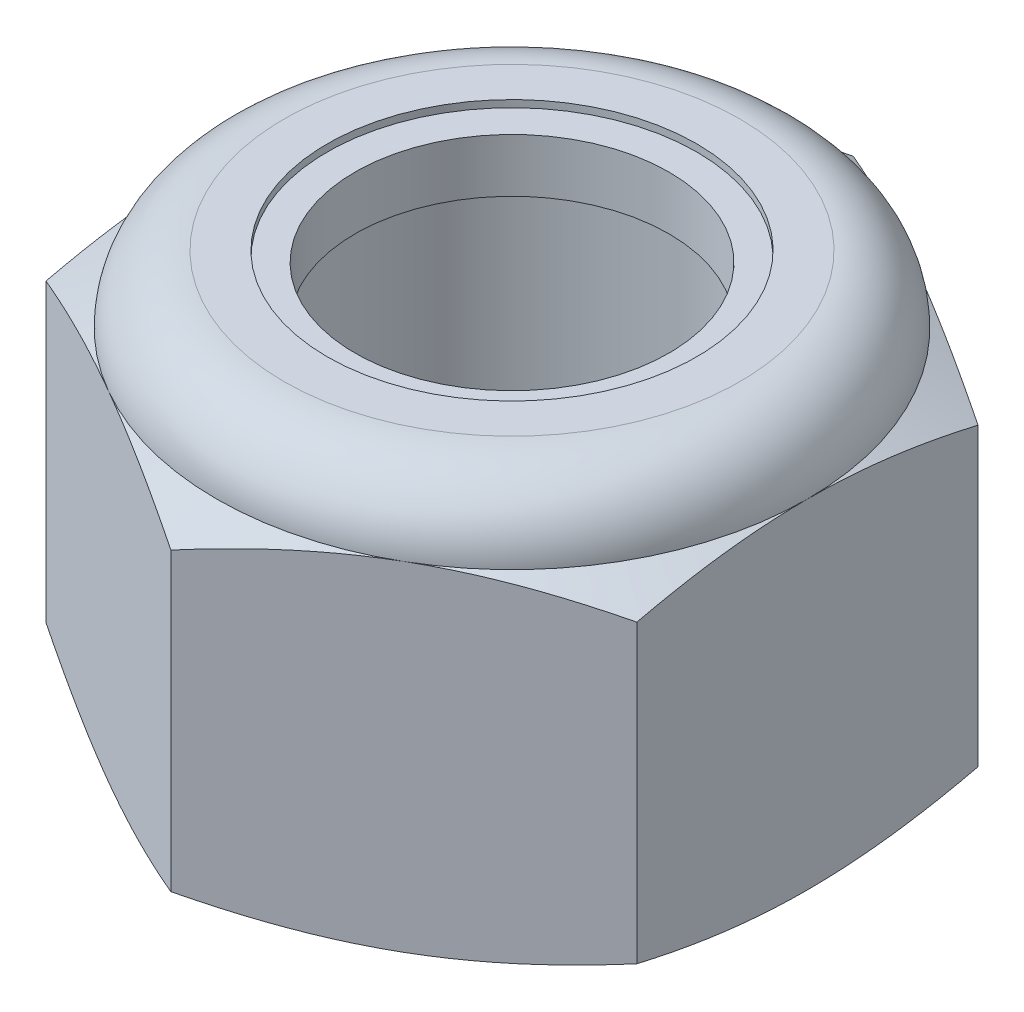
SolidWorks part; units mm, degrees
ref_plane "Front" through (0, 0, 0) normal (0, 0, 1) x (1, 0, 0)
ref_plane "Top" through (0, 0, 0) normal (0, 1, 0) x (1, 0, 0)
ref_plane "Right" through (0, 0, 0) normal (1, 0, 0) x (0, 0, -1)
sketch "Sketch1" plane through (0, 0, 0) normal (1, 0, 0) x (0, 0, -1)
  line L0 (0, 0) -> (0, 8.7312) construction
  line L1 (6.35, 0) -> (-6.35, 0) construction
  line L2 (-3.9688, 8.7312) -> (3.9688, 8.7312) construction
  line L3 (3.9688, 8.7312) -> (3.9687, 7.6729) construction
  point P9 (-3.9688, 8.7312)
  point P10 (3.9688, 8.7312)
  point P11 (6.35, 0)
  dimension "Height" = 8.7312
  dimension "Hex Flats" = 12.7
  dimension "Thread Dia" = 7.9375
  dimension "Thread Pitch" = 1.0583
sketch "Sketch13" plane through (0, 0, 0) normal (0, 1, 0) x (1, 0, 0)
  line L1 (0, 7.3323) -> (-6.35, 3.6662)
  line L2 (-6.35, 3.6662) -> (-6.35, -3.6662)
  line L3 (-6.35, -3.6662) -> (0, -7.3323)
  line L4 (0, -7.3323) -> (6.35, -3.6662)
  line L5 (6.35, -3.6662) -> (6.35, 3.6662)
  line L6 (6.35, 3.6662) -> (0, 7.3323)
  circle A0 centre (0, 0) radius 6.35 construction
  circle A1 centre (0, 0) radius 3.9688
  point P11 (0, -3.9688)
  point P13 (0, 3.9688)
extrude "Extrude1" add sketch "Sketch13" along normal up to vertex (8.7312 mm away) up to point (0, 8.7312, 0)
sketch "Sketch5" plane through (0, 0, 0) normal (1, 0, 0) x (0, 0, -1)
  line L0 (0, 0) -> (6.35, 0)
  line L1 (6.35, 0) -> (7.3323, 0.4581)
  line L2 (7.3323, 0.4581) -> (7.3323, 6.818)
  line L3 (7.3323, 6.818) -> (6.35, 7.276)
  line L4 (4.8948, 8.7312) -> (4.8948, 10.0013)
  line L5 (4.8948, 10.0013) -> (8.6023, 10.0013)
  line L6 (8.6023, 10.0013) -> (8.6023, -1.27)
  line L7 (8.6023, -1.27) -> (0, -1.27)
  line L8 (0, -1.27) -> (0, 0)
  line L9 (6.35, 7.276) -> (6.35, 0) construction
  line L12 (7.3323, 8.7312) -> (7.3323, 0) construction
  line L13 (7.3323, 4.3656) -> (8.6023, 4.3656) construction
  line L15 (0, 0) -> (0, 10.0013) construction
  line L18 (6.35, 0) -> (-6.35, 0) construction
  line L19 (3.6662, 8.7312) -> (7.3323, 8.7312) construction
  line L20 (0, 10.0013) -> (4.8948, 10.0013) construction
  line L21 (3.6662, 0) -> (7.3323, 0) construction
  arc A0 (6.35, 7.276) -> (4.8948, 8.7312) centre (4.8948, 7.276) ccw
  dimension "D1" = 25
  dimension "D2" = 1.27
  dimension "D4" = 1.4552
revolve "Cut-Revolve3" cut sketch "Sketch5" angle 360 about L15
sketch "Sketch4" plane through (0, 0, 0) normal (1, 0, 0) x (0, 0, -1)
  line L0 (0, 7.276) -> (4.3656, 7.276)
  line L1 (4.3656, 7.276) -> (0, 5.2403)
  line L3 (0, 2.0357) -> (4.3656, 0)
  line L4 (4.3656, 0) -> (0, 0)
  line L5 (0, 0) -> (0, 7.276) construction
  line L10 (0, 0) -> (0, 8.7312) construction
  line L11 (0, 2.0357) -> (0, 0)
  line L12 (0, 7.276) -> (0, 5.2403)
  line L13 (5.4993, 7.276) -> (0, 7.276) construction
  dimension "D1" = 25
  dimension "D2" = 8.7312
sketch "Sketch6" plane through (0, 0, 0) normal (1, 0, 0) x (0, 0, -1)
  line L0 (0, 7.276) -> (6.1976, 7.276)
  line L1 (4.8948, 8.5788) -> (2.4474, 8.5788)
  line L2 (0, 10.0013) -> (0, 7.276)
  line L3 (2.4474, 10.0013) -> (0, 10.0013)
  line L4 (0, 10.0013) -> (4.8948, 10.0013) construction
  line L5 (0, 0) -> (0, 10.0013) construction
  line L6 (0, 10.0013) -> (0, 0) construction
  line L7 (2.4474, 8.5788) -> (2.4474, 10.0013)
  line L8 (4.8948, 8.7312) -> (4.8948, 8.5788) construction
  line L9 (2.4474, 8.5788) -> (0, 8.5788) construction
  line L10 (0, 8.5788) -> (0, 5.2403) construction
  arc A0 (6.1976, 7.276) -> (4.8948, 8.5788) centre (4.8948, 7.276) ccw
  arc A1 (6.35, 7.276) -> (4.8948, 8.7312) centre (4.8948, 7.276) ccw construction
  dimension "D1" = 0.1524
revolve "Cut-Revolve4" cut sketch "Sketch6" angle 360 about L6
revolve "Cut-Revolve2" cut sketch "Sketch4" angle 360 about L5
sketch "Sketch7" plane through (0, 0, 0) normal (1, 0, 0) x (0, 0, -1)
  line L0 (3.3734, 7.3522) -> (6.119, 7.3522)
  line L1 (4.8948, 8.5027) -> (3.3734, 8.5027)
  line L2 (3.3734, 8.5027) -> (3.3734, 7.3522)
  line L3 (3.3734, 7.3522) -> (0, 7.3522) construction
  line L4 (0, 7.3522) -> (0, 8.5027) construction
  line L5 (0, 8.5027) -> (3.3734, 8.5027) construction
  line L6 (3.3734, 7.3522) -> (3.3734, 7.276) construction
  line L7 (0, 7.276) -> (6.1976, 7.276) construction
  line L8 (4.8948, 8.5027) -> (4.8948, 8.5788) construction
  arc A0 (6.119, 7.3522) -> (4.8948, 8.5027) centre (4.8948, 7.276) ccw
  arc A2 (6.1976, 7.276) -> (4.8948, 8.5788) centre (4.8948, 7.276) ccw construction
  point P15 (3.3734, 8.5027)
  point P18 (-4.1341, 8.5027)
  point P19 (4.1341, 8.5027)
  dimension "D2" = 6.7469
revolve "Revolve2" add sketch "Sketch7" angle 360 about L4
sketch "Sketch2" [suppressed] plane through (0, 0, 0) normal (1, 0, 0) x (0, 0, -1)
  line L0 (-3.9688, 0) -> (-3.9688, 7.276) construction
  line L1 (0, 0) -> (3.9688, 0)
  line L2 (0, 0) -> (0, 7.276)
  line L3 (0, 7.276) -> (3.9688, 7.276)
  line L4 (3.9688, 0) -> (3.9688, 7.276)
  line L6 (5.4993, 7.276) -> (6.35, 7.276) construction
  line L7 (0, -3.9688) -> (0, 0) construction
revolve "Revolve1" [suppressed] add sketch "Sketch2" angle 360 about L7
sketch "Sketch9" [suppressed] plane through (0, 0, 0) normal (1, 0, 0) x (0, 0, -1)
  line L0 (4.0833, 8.2682) -> (4.0833, 7.2099) construction
  line L1 (4.0833, 7.2099) -> (3.1668, 7.7391) construction
  line L2 (3.1668, 7.7391) -> (4.0833, 8.2682) construction
  line L3 (3.2813, 7.8052) -> (3.2813, 7.6729) construction
  line L4 (3.9688, 8.2021) -> (3.9688, 7.276) construction
  line L5 (3.1668, 7.7391) -> (3.2813, 7.7391) construction
  line L6 (3.9688, 7.7391) -> (4.0833, 7.7391) construction
  line L7 (4.026, 7.7391) -> (4.026, 8.2352) construction
  line L8 (4.0833, 7.2099) -> (4.026, 8.2352)
  line L9 (4.026, 8.2352) -> (3.2813, 7.8052)
  line L10 (3.2813, 7.8052) -> (3.2813, 7.6729)
  line L11 (3.2813, 7.6729) -> (4.0833, 7.2099)
  dimension "D1" = 1.0583
  dimension "D2" = 0.1323
sketch "Sketch10" [suppressed] plane through (0, 7.276, 0) normal (0, 1, 0) x (1, 0, 0)
  circle A1 centre (0, 0) radius 3.9688
  circle A2 centre (0, 0) radius 3.9688
  dimension "D1" = 0
curve "Helix/Spiral1" [suppressed] pitch 1.0583 height 9.7896 turns 9.25
sweep "Cut-Sweep1" [suppressed] cut profiles "Sketch9" path "Helix/Spiral1"
sketch "Sketch11" [suppressed] plane through (0, 0, 0) normal (1, 0, 0) x (0, 0, -1)
  line L0 (0, 0) -> (0, 8.7312) construction
  line L1 (6.35, 0) -> (-6.35, 0) construction
  line L4 (0, 8.7312) -> (0, 0) construction
  line L5 (0, 4.3656) -> (3.9688, 4.3656) construction
  line L6 (0, 0) -> (4.3656, 0)
  line L7 (0, 2.0357) -> (0, 0)
  line L8 (4.3656, 0) -> (0, 2.0357)
  dimension "D1" = 8.7312
  dimension "D2" = 25
revolve "Revolve3" [suppressed] add sketch "Sketch11" angle 360 about L4
sketch "Sketch12" [suppressed] plane through (0, 0, 0) normal (1, 0, 0) x (0, 0, -1)
  line L0 (4.3656, 7.276) -> (0, 7.276)
  line L1 (0, 7.276) -> (0, 0)
  line L2 (0, 0) -> (4.3656, 0)
  line L3 (6.35, 0) -> (-6.35, 0) construction
  line L4 (4.3656, 0) -> (4.3656, 7.276)
  line L5 (-4.3656, 0) -> (4.3656, 0) construction
revolve "Revolve4" [suppressed] add sketch "Sketch12" angle 360 about L0
combine bodies "Combine1" [suppressed] operation type subtract main body 136 bodies to subtract 133
equation "\"D4@Sketch5\" = \"Height@Sketch1\" / 6"
equation "\"D1@Sketch9\" = \"Thread Pitch@Sketch1\""
equation "\"D2@Sketch9\" = \"Thread Pitch@Sketch1\" / 8"
equation "\"D4@Helix/Spiral1\" = \"Thread Pitch@Sketch1\""
equation "\"D3@Helix/Spiral1\" = \"Thread Pitch@Sketch1\" + \"Height@Sketch1\""
equation "\"D2@Sketch4\" = \"Thread Dia@Sketch1\" * 1.1"
equation "\"D1@Sketch11\" = \"Thread Dia@Sketch1\" * 1.1"
equation "\"D2@Sketch7\" = \"Thread Dia@Sketch1\" * .85"
